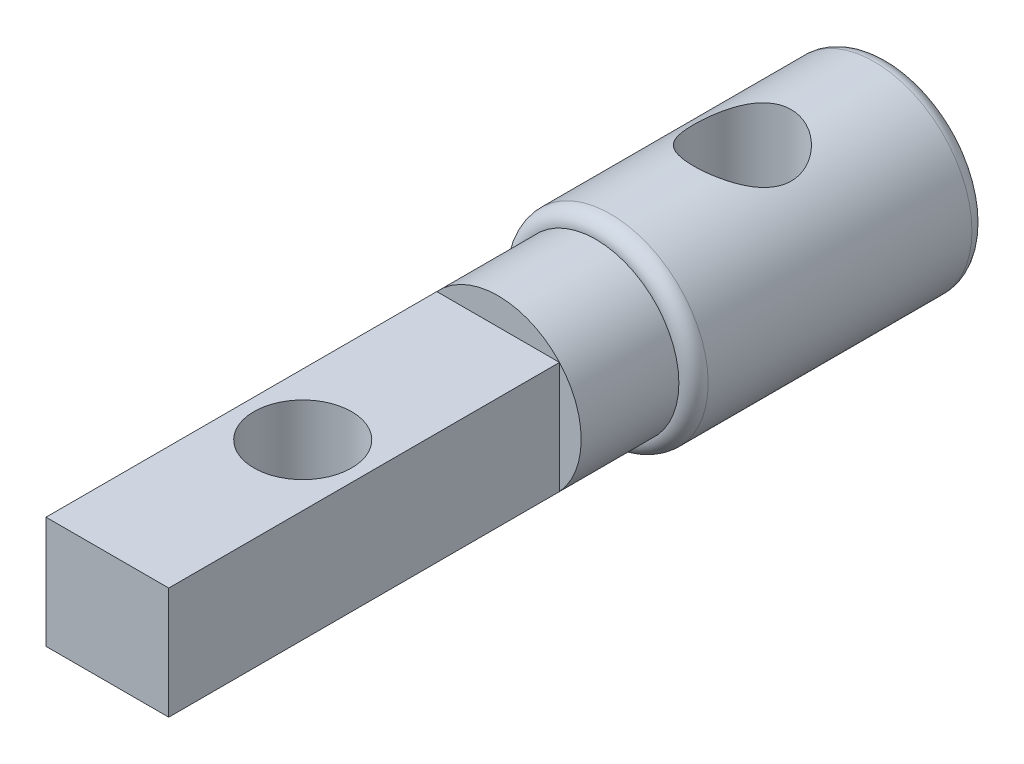
SolidWorks part; units mm, degrees
ref_plane "Front Plane" through (0, 0, 0) normal (0, 0, 1) x (1, 0, 0)
ref_plane "Top Plane" through (0, 0, 0) normal (0, 1, 0) x (1, 0, 0)
ref_plane "Right Plane" through (0, 0, 0) normal (1, 0, 0) x (0, 0, -1)
sketch "Sketch1" plane through (0, 0, 0) normal (0, 0, 1) x (1, 0, 0)
  circle A0 centre (0, 0) radius 20
  dimension "D1" = 40
extrude "Boss-Extrude1" add sketch "Sketch1" along normal blind 60
sketch "Sketch2" plane through (0, 0, 0) normal (0, 1, 0) x (1, 0, 0)
  circle A0 centre (0, -30) radius 10
  dimension "D1" = 20
extrude "Cut-Extrude1" cut sketch "Sketch2" against normal through all and the other way through all
fillet "Fillet1" radius 3 2 edges at (20, 0, 0) (20, 0, 60)
sketch "Sketch19" plane through (0, 0, 0) normal (0, 1, 0) x (1, 0, 0)
  line L0 (0, -30) -> (69.3072, -30) construction
  circle A1 centre (0, -120) radius 10
  dimension "D1" = 20
sketch "Sketch22" plane through (0, 0, 60) normal (0, 0, 1) x (1, 0, 0)
  circle A0 centre (0, 0) radius 17
extrude "Boss-Extrude4" add sketch "Sketch22" along normal blind 100
extrude "Cut-Extrude4" cut sketch "Sketch19" against normal blind 100 and the other way blind 100
sketch "Sketch23" plane through (0, 0, 160) normal (0, 0, 1) x (1, 0, 0)
  line L1 (-12.5627, 11.4534) -> (12.5627, 11.4534)
  line L2 (-12.5627, 11.4534) -> (-12.5627, -11.4534)
  line L3 (-12.5627, -11.4534) -> (12.5627, -11.4534)
  line L4 (12.5627, 11.4534) -> (12.5627, -11.4534)
  line L5 (-12.5627, 11.4534) -> (12.5627, -11.4534) construction
  line L6 (-12.5627, -11.4534) -> (12.5627, 11.4534) construction
  circle A0 centre (0, 0) radius 17 construction
  circle A1 centre (0, 0) radius 17
  point P0 (0, 0)
  circle M1 centre (0, 0) radius 17
extrude "Cut-Extrude5" cut sketch "Sketch23" against normal blind 80 contours L1 M1 | L2 M1 | L3 M1 | L4 M1 region at (0, 13.7063, 160) region at (-14.3591, 0, 160) region at (14.3591, 0, 160) region at (0, -13.7063, 160)
